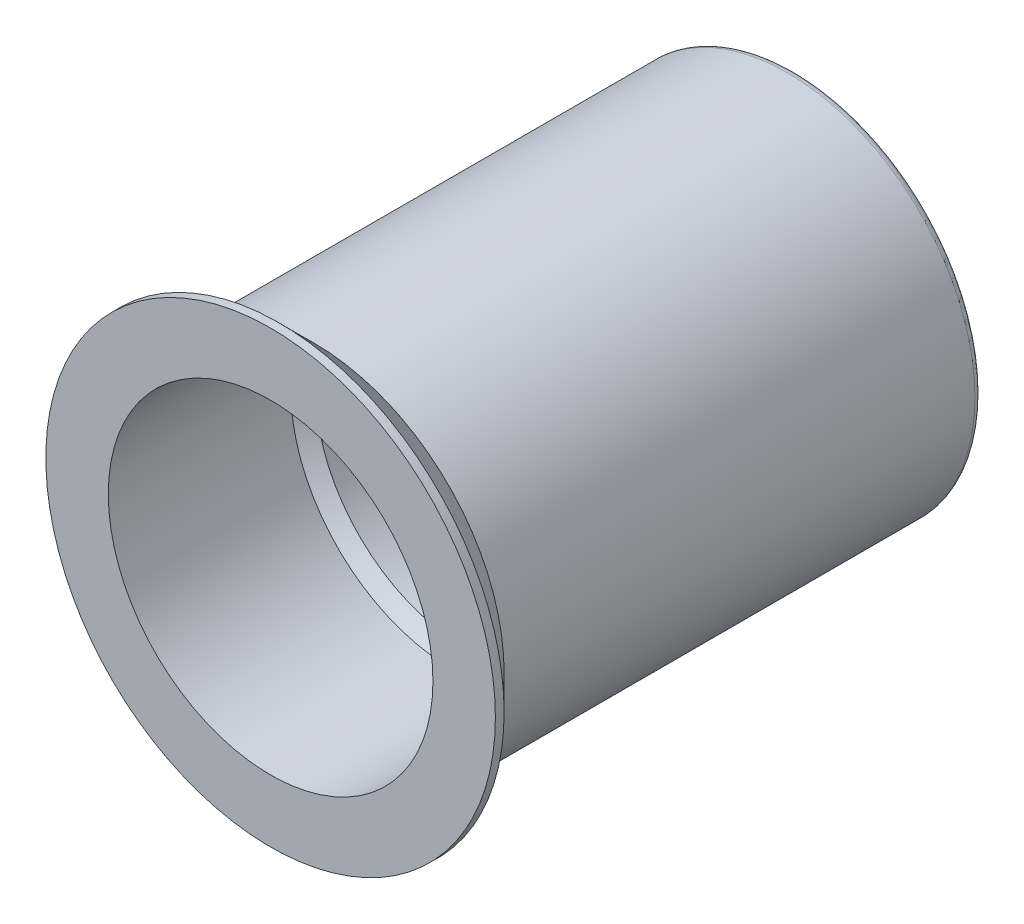
SolidWorks part; units mm, degrees
ref_plane "Front" through (0, 0, 0) normal (0, 0, 1) x (1, 0, 0)
ref_plane "Top" through (0, 0, 0) normal (0, 1, 0) x (1, 0, 0)
ref_plane "Right" through (0, 0, 0) normal (1, 0, 0) x (0, 0, -1)
sketch "Sketch3" plane through (0, 0, 0) normal (0, 0, 1) x (1, 0, 0)
  circle A0 centre (0, 0) radius 9
  dimension "dk" = 18
extrude "BaseHead" add sketch "Sketch3" against normal blind 1.8
sketch "Sketch4" plane through (-3.067, 2.6488, 0) normal (0, 0, -1) x (-1, 0, 0)
  circle A0 centre (-3.067, -2.6488) radius 7.5
  circle A1 centre (-3.067, -2.6488) radius 9 construction
extrude "BaseBody" add sketch "Sketch4" along normal blind 21
sketch "Sketch8" plane through (9, 0, 1.1855) normal (0, 1, 0) x (-1, 0, 0)
  line L0 (9, 2.3542) -> (9, -3.5397) construction
  line L2 (18, -1.5355) -> (16.55, -2.9855)
  line L5 (16.55, -2.9855) -> (18, -2.9855)
  line L7 (18, -2.9855) -> (18, -1.5355)
  dimension "D1" = 45
  dimension "D2" = 15.1
revolve "BearingFace" cut sketch "Sketch8" angle 360 about L0
sketch "Sketch5" plane through (1.6426, -1.4193, 0) normal (0, 0, 1) x (1, 0, 0)
  circle A0 centre (-1.6426, 1.4193) radius 6.5
  circle A1 centre (-1.6426, 1.4193) radius 9 construction
extrude "Hole1" cut sketch "Sketch5" against normal blind 7.3
sketch "Sketch6" plane through (-0.0097, -0.1511, -7.3) normal (0, 0, 1) x (1, 0, 0)
  circle A0 centre (0.0097, 0.1511) radius 6
  circle A1 centre (0.0097, 0.1511) radius 6.5 construction
  dimension "D1" = 12
extrude "Hole2" cut sketch "Sketch6" against normal through all
cosmetic thread "ThreadCosmetic1" [suppressed] parameters "D2"=13
fillet "Fillet1" radius 0.3 2 edges at (-7.5, 0, -21) (7.55, 0, -1.8)
chamfer "Chamfer1" distance 0.5 angle 45 1 edges at (6, 0, -7.3)
chamfer "Chamfer2" distance 0.48 angle 45 1 edges at (6, 0, -21)
sketch "Sketch9" plane through (0, 0, 0) normal (0, 1, 0) x (1, 0, 0)
  line L0 (0, 24.077) -> (0, 16.4991) construction
  line L1 (5.5, 20.77) -> (6, 20.77)
  line L2 (6, 20.77) -> (6.433, 20.52)
  line L3 (6.433, 20.52) -> (6, 20.27)
  line L4 (6, 20.27) -> (5.5, 20.27)
  line L5 (5.5, 20.27) -> (5.5, 20.77)
  line L6 (-6, 20.52) -> (6, 20.52) construction
  dimension "D2" = 12
revolve "Cut-Revolve10" [suppressed] cut sketch "Sketch9" angle 360 about L0
pattern_linear "LPattern10" [suppressed] count 23 spacing 0.6 along (0, 0, 1) of bodies 107
equation "\"D2@Sketch8\"=\"d@Sketch4\"+ 0.1"
equation "\"D1@Chamfer1\" =  ( \"d1@Sketch5\" - \"D1@Sketch6\" )  / 2"
equation "\"D1@Chamfer2\" = \"D1@Sketch6\" / 25"
equation "\"D2@Sketch9\" = \"D1@Sketch6\""
equation "\"D1@Sketch9\" = (  \"D2@ThreadCosmetic1\" - \"D1@Sketch6\" )  / 2"
equation "\"D3@LPattern10\" = \"D1@Sketch9\" * 1.2"
equation "\"D1@LPattern10\" = (  \"l@BaseBody\" - \"l1@Hole1\" )  / \"D3@LPattern10\""
